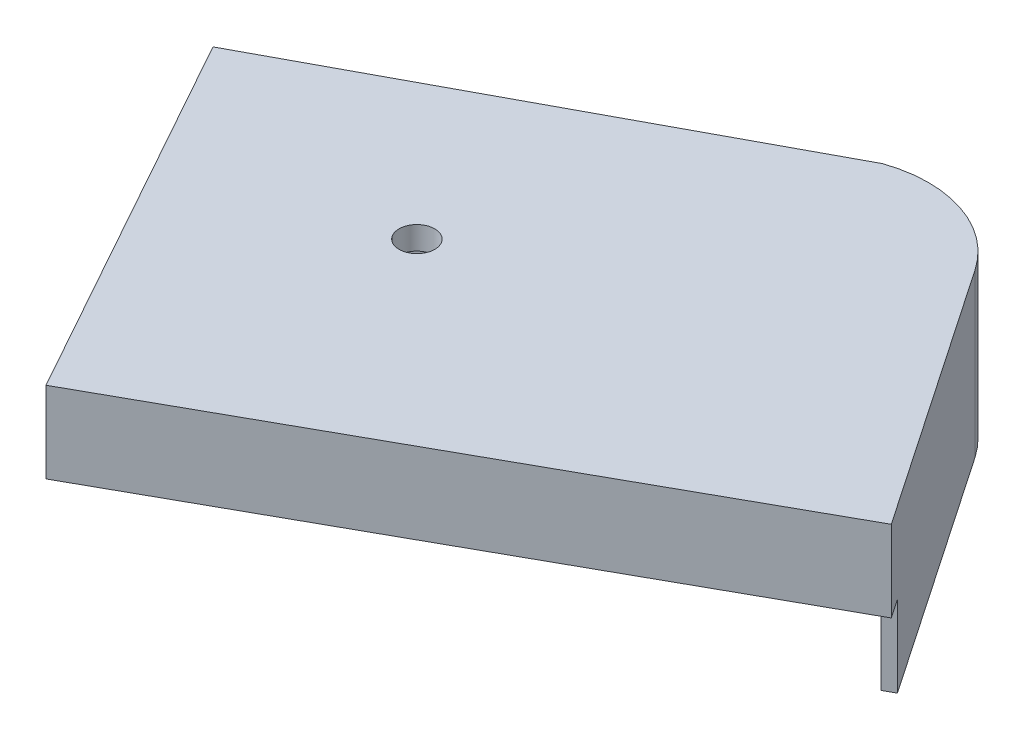
SolidWorks part; units mm, degrees
ref_plane "Front Plane" through (0, 0, 0) normal (0, 0, 1) x (1, 0, 0)
ref_plane "Top Plane" through (0, 0, 0) normal (0, 1, 0) x (1, 0, 0)
ref_plane "Right Plane" through (0, 0, 0) normal (1, 0, 0) x (0, 0, -1)
sketch "Sketch1" plane through (0, 0, 0) normal (0, 1, 0) x (1, 0, 0)
  line L0 (94.9289, -1.7036) -> (55.5294, 56.1873)
  line L1 (94.9289, -1.7036) -> (-24.9201, -68.405)
  line L2 (-24.9201, -68.405) -> (-71.1661, 14.6897)
  line L3 (24.9907, 66.236) -> (-71.1661, 14.6897)
  line L4 (26.052, 63.8122) -> (-67.5582, 13.631)
  line L5 (-23.8981, -64.8175) -> (-67.5582, 13.631)
  line L6 (91.1247, -0.8021) -> (-23.8981, -64.8175)
  line L7 (91.1247, -0.8021) -> (53.3488, 54.7032)
  arc A0 (55.5294, 56.1873) -> (24.9907, 66.236) centre (33.7235, 41.3467) ccw
  arc A1 (53.3488, 54.7032) -> (26.052, 63.8122) centre (33.7235, 41.3467) ccw
  dimension "D1" = 137.16
extrude "Boss-Extrude1" add sketch "Sketch1" along normal blind 35.814 contours L0 A0 L3 L2 L1
extrude "Cut-Extrude1" cut sketch "Sketch1<6>" along normal blind 30.734 contours L6 L5 L4 A1 L7
sketch "Sketch1<6>" plane through (0, 0, 0) normal (0, 1, 0) x (1, 0, 0) same geometry as "Sketch1"
sketch "Sketch5" plane through (0, 35.814, 0) normal (0, 1, 0) x (1, 0, 0)
  line L0 (94.9289, -1.7036) -> (-24.9201, -68.405) construction
  line L1 (94.9289, -1.7036) -> (55.5294, 56.1873) construction
  circle A0 centre (-11.9242, 0.4536) radius 3.937
  dimension "D1" = 7.874
  dimension "D2" = 53.848
  dimension "D3" = 87.122
extrude "Cut-Extrude2" cut sketch "Sketch5" against normal blind 12.7
sketch "Sketch7" plane through (23.1738, 0, 41.6386) normal (0.4863, 0, 0.8738) x (0.8738, 0, -0.4863)
  line L0 (82.1194, 35.814) -> (82.1194, 0) construction
  line L1 (-55.0406, 0) -> (82.1194, 0)
  line L2 (-55.0406, 0) -> (-55.0406, 17.907)
  line L3 (-55.0406, 17.907) -> (82.1194, 17.907)
  line L4 (82.1194, 0) -> (82.1194, 17.907)
extrude "Cut-Extrude3" cut sketch "Sketch7" against normal blind 5.08
sketch "Sketch8" plane through (-48.0939, 0, 26.7664) normal (-0.8738, 0, 0.4863) x (0.4863, 0, 0.8738)
  line L0 (-47.4441, 35.814) -> (-47.4441, 0) construction
  line L1 (42.5729, 0) -> (-47.4441, 0)
  line L2 (42.5729, 0) -> (42.5729, 17.907)
  line L3 (42.5729, 17.907) -> (-47.4441, 17.907)
  line L4 (-47.4441, 0) -> (-47.4441, 17.907)
  point P7 (-45.6869, 0)
  point P9 (-45.6869, 0)
  point P10 (-45.6869, 0)
extrude "Cut-Extrude4" cut sketch "Sketch8" against normal blind 5.08 contours L2 L1 L4 L3
sketch "Sketch9" plane through (0, 35.814, 0) normal (0, 1, 0) x (1, 0, 0)
